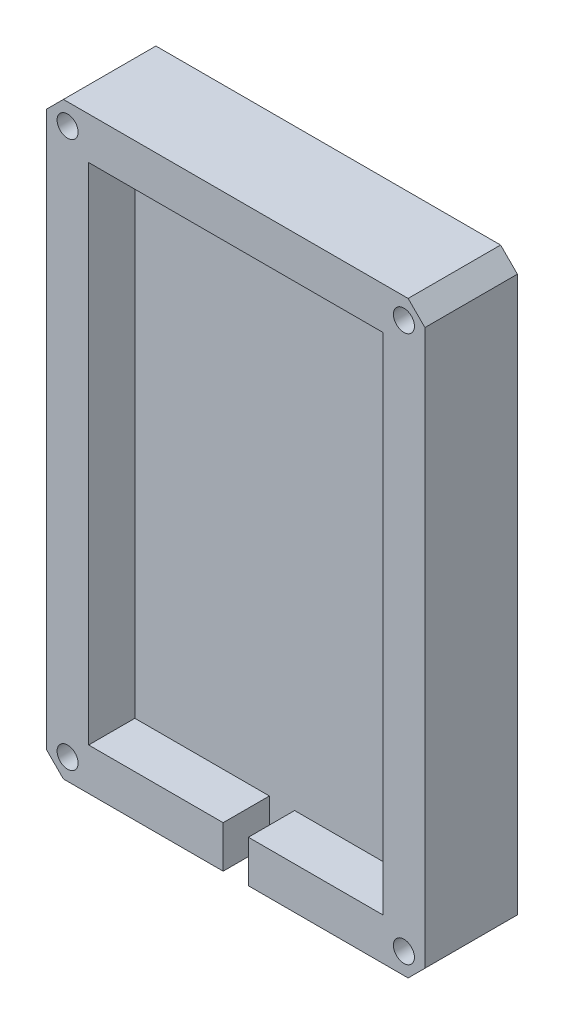
SolidWorks part; units mm, degrees
ref_plane "Front Plane" through (0, 0, 0) normal (0, 0, 1) x (1, 0, 0)
ref_plane "Top Plane" through (0, 0, 0) normal (0, 1, 0) x (1, 0, 0)
ref_plane "Right Plane" through (0, 0, 0) normal (1, 0, 0) x (0, 0, -1)
sketch "Sketch1" plane through (0, 0, 0) normal (0, 0, 1) x (1, 0, 0)
  line L0 (22.5, -35) -> (22.5, 35)
  line L1 (-17.5, -30) -> (17.5, -30)
  line L2 (-17.5, -30) -> (-17.5, 30)
  line L3 (-17.5, 30) -> (17.5, 30)
  line L4 (17.5, -30) -> (17.5, 30)
  line L5 (-17.5, -30) -> (17.5, 30) construction
  line L6 (-17.5, 30) -> (17.5, -30) construction
  line L7 (-22.5, 35) -> (22.5, 35)
  line L8 (-22.5, -35) -> (-22.5, 35)
  line L9 (-22.5, -35) -> (22.5, -35)
  line L10 (0, -35) -> (0, -30) construction
  line L11 (-1.5, -30) -> (-1.5, -35)
  line L12 (1.5, -30) -> (1.5, -35)
  line L13 (-20, -32.5) -> (-20, 32.5) construction
  line L14 (-20, 32.5) -> (20, 32.5) construction
  line L15 (20, -32.5) -> (20, 32.5) construction
  line L16 (-20, -32.5) -> (20, -32.5) construction
  point P0 (0, 0)
  dimension "D1" = 60
  dimension "D2" = 35
  dimension "D4" = 3
  dimension "D3" = 5
  dimension "D5" = 2.5
extrude "Boss-Extrude1" add sketch "Sketch1" along normal blind 5.5 contours L1 L12 L9 L0 L7 L8 L11 L2 L3 L4 region at (12, -34.1678, 0)
extrude "Boss-Extrude2" add sketch "Sketch1<3>" against normal blind 5.5 contours L1 L12 L9 L0 L7 L8 L11 L2 L3 L4 | L1 L4 L3 L2 | L12 L1 L11 L9 region at (12, -34.1678, 0) region at (0, -32.5, 0) region at (0, 0, 0)
sketch "Sketch1<3>" plane through (0, 0, 0) normal (0, 0, 1) x (1, 0, 0) same geometry as "Sketch1"
sketch "Sketch2" plane through (0, 0, -5.5) normal (0, 0, -1) x (-1, 0, 0)
  point P0 (20, 32.5)
  point P3 (-20, 32.5)
  point P6 (-20, -32.5)
  point P9 (20, -32.5)
hole_wizard "Tap Drill for M3 Tap1" positions "Sketch2" profile "Sketch3" hole size "M3" standard "ISO" end condition through all
sketch "Sketch3" plane through (-20, 32.5, -5.5) normal (1, 0, 0) x (0, 1, 0)
  line L0 (0, 0) -> (0, 11)
  line L1 (0, 11) -> (1.25, 11)
  line L2 (1.25, 11) -> (1.25, 0.025)
  line L3 (1.25, 0.025) -> (1.275, 0)
  line L5 (1.275, 0) -> (0, 0)
  line L6 (-1.25, 0.025) -> (-1.275, 0) construction
  line L11 (0, -6.35) -> (0, 107.95) construction
  dimension "Thru Hole Dia." = 2.5
  dimension "Thru Hole Depth" = 11
  dimension "Near C'Sink Dia." = 2.55
  dimension "Near C'Sink Angle" = 90
chamfer "Chamfer1" distance 2 angle 45 4 edges at (22.5, -35, 0) (22.5, 35, 0) (-22.5, 35, 0) (-22.5, -35, 0)
